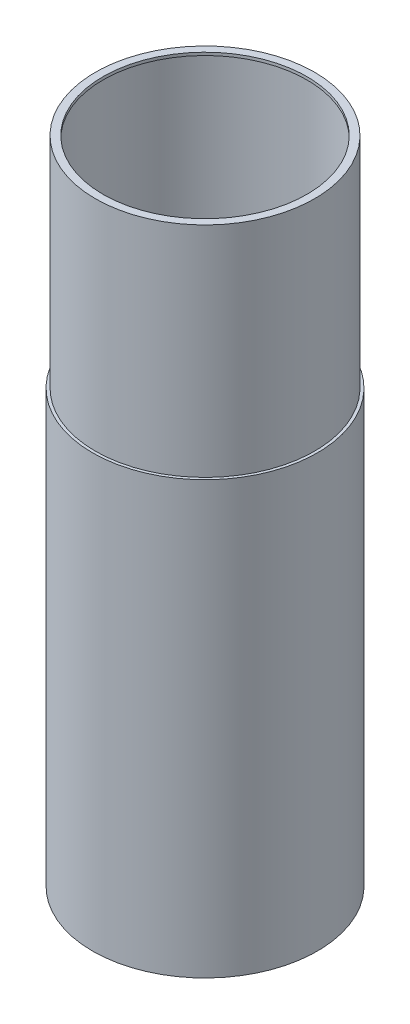
SolidWorks part; units mm, degrees
material "A-Glass Fiber"
ref_plane "Front Plane" through (0, 0, 0) normal (0, 0, 1) x (1, 0, 0)
ref_plane "Top Plane" through (0, 0, 0) normal (0, 1, 0) x (1, 0, 0)
ref_plane "Right Plane" through (0, 0, 0) normal (1, 0, 0) x (0, 0, -1)
sketch "Sketch1" plane through (0, 0, 0) normal (0, 0, 1) x (1, 0, 0)
  line L0 (78.16, 0) -> (78.16, 300)
  line L1 (76.2, 0) -> (76.2, 300)
  line L2 (78.16, 300) -> (76.2, 300)
  line L3 (76.2, 0) -> (78.16, 0)
  line L4 (0, 204.6154) -> (0, 85.8935) construction
  dimension "D1" = 76.2
  dimension "D2" = 300
  dimension "D3" = 1.96
revolve "Revolve1" add sketch "Sketch1" angle 360 about L4
sketch "Sketch3" plane through (0, 300, 0) normal (0, 1, 0) x (1, 0, 0)
  circle A2 centre (0, 0) radius 76.2 construction
  circle A3 centre (0, 0) radius 76.2
  circle A4 centre (0, 0) radius 75.2
  dimension "D1" = 1
extrude "Boss-Extrude1" add sketch "Sketch3" along normal blind 152 and the other way blind 152
sketch "Sketch4" plane through (0, 452, 0) normal (0, 1, 0) x (1, 0, 0)
  circle A0 centre (0, 0) radius 76.2
  circle A1 centre (0, 0) radius 70.915
extrude "Boss-Extrude2" add sketch "Sketch4" against normal blind 2
